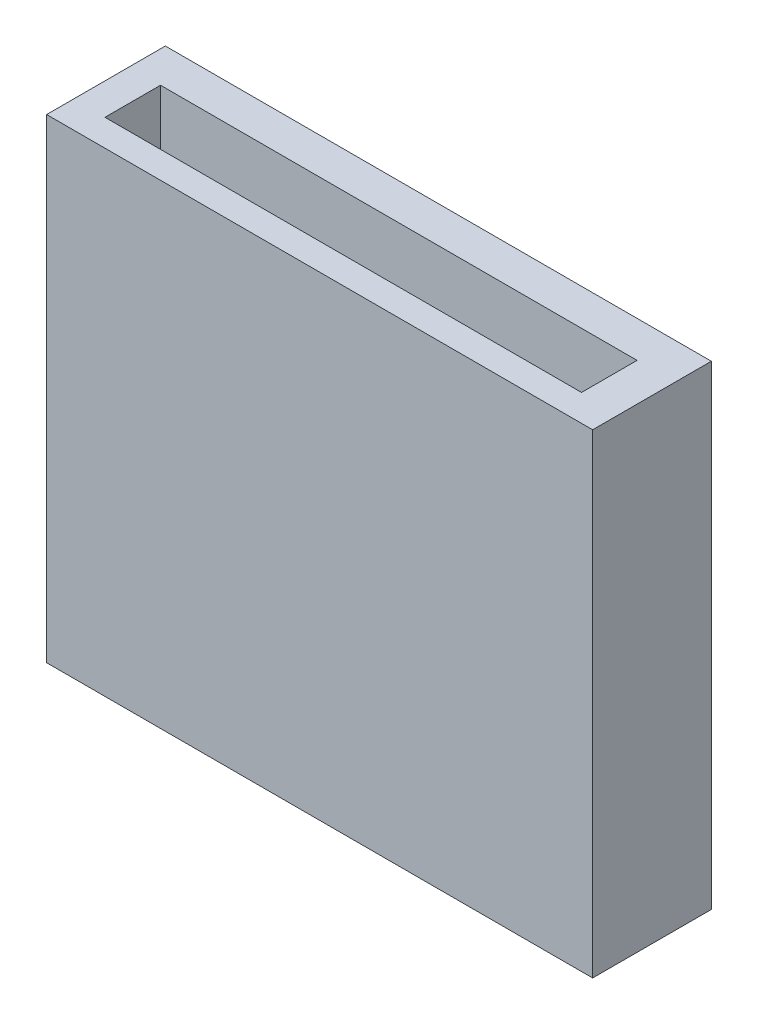
SolidWorks part; units mm, degrees
ref_plane "Front Plane" through (0, 0, 0) normal (0, 0, 1) x (1, 0, 0)
ref_plane "Top Plane" through (0, 0, 0) normal (0, 1, 0) x (1, 0, 0)
ref_plane "Right Plane" through (0, 0, 0) normal (1, 0, 0) x (0, 0, -1)
sketch "Sketch1" plane through (0, 0, 0) normal (0, 1, 0) x (1, 0, 0)
  line L1 (0, 0) -> (46, 0)
  line L2 (0, 0) -> (0, 10)
  line L3 (0, 10) -> (46, 10)
  line L4 (46, 0) -> (46, 10)
extrude "Boss-Extrude1" add sketch "Sketch1" along normal blind 40
sketch "Sketch3" plane through (0, 40, 0) normal (0, 1, 0) x (1, 0, 0)
  line L1 (2.6574, 2.2546) -> (42.8074, 2.2546)
  line L2 (2.6574, 2.2546) -> (2.6574, 6.9346)
  line L3 (2.6574, 6.9346) -> (42.8074, 6.9346)
  line L4 (42.8074, 2.2546) -> (42.8074, 6.9346)
  line L5 (2.6574, 2.2546) -> (42.8074, 6.9346) construction
  line L6 (2.6574, 6.9346) -> (42.8074, 2.2546) construction
  point P0 (22.7324, 4.5946)
  dimension "D1" = 40.15
  dimension "D2" = 4.68
extrude "Cut-Extrude1" cut sketch "Sketch3" against normal up to surface (40 mm away) up to face at (23, 0, -5)
